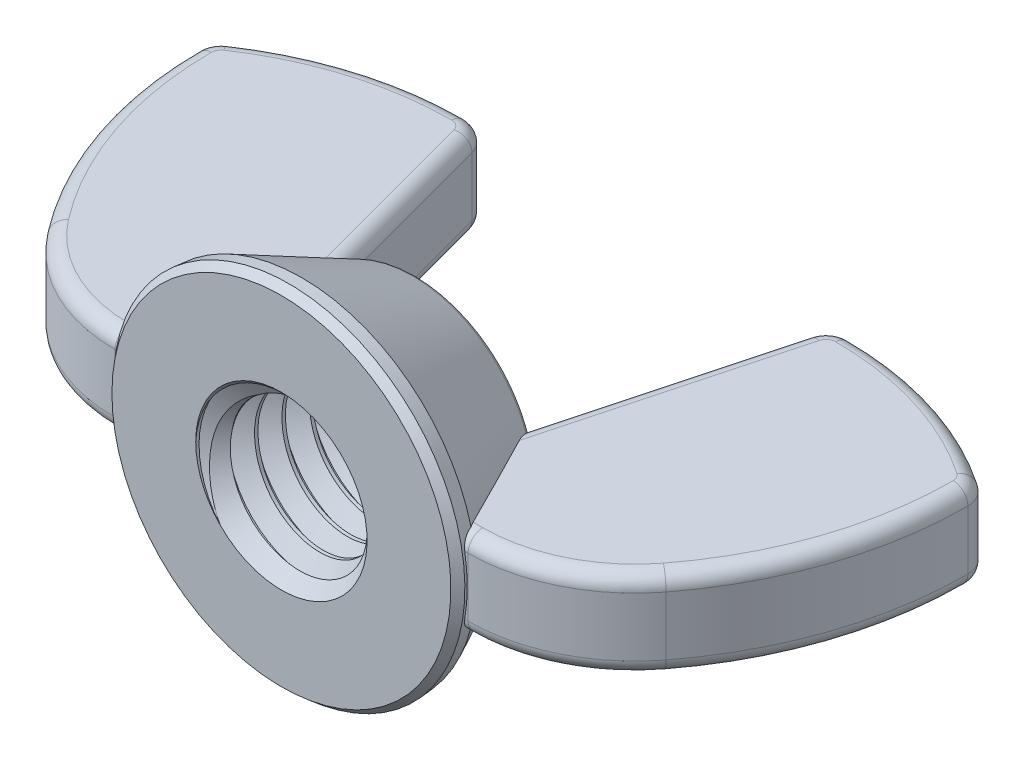
SolidWorks part; units mm, degrees
ref_plane "Front Plane" through (0, 0, 0) normal (0, 0, 1) x (1, 0, 0)
ref_plane "Top Plane" through (0, 0, 0) normal (0, 1, 0) x (1, 0, 0)
ref_plane "Right Plane" through (0, 0, 0) normal (1, 0, 0) x (0, 0, -1)
sketch "Sketch1" plane through (0, 0, 0) normal (0, 0, 1) x (1, 0, 0)
  circle A0 centre (0, 0) radius 2.5
  circle A1 centre (0, 0) radius 5.15
  dimension "D1" = 10.3
sketch "Sketch2" plane through (0, 0, 0) normal (0, 1, 0) x (1, 0, 0)
  line L0 (0, 0) -> (0, 11) construction
  line L1 (-2.5, 0) -> (2.5, 0) construction
  line L2 (-11.25, 11) -> (11.25, 11) construction
  line L3 (11.25, 11) -> (11.25, 0) construction
  line L4 (-11.25, 11) -> (-11.25, 0) construction
  line L5 (-11.25, 0) -> (11.25, 0) construction
  line L6 (-3.5176, 3.96) -> (3.5176, 3.96) construction
  line L7 (0, 0) -> (0, 3.96) construction
  line L8 (-4.3144, 0.594) -> (5.15, 0.594) construction
  line L9 (5.15, 0) -> (5.15, 3.96) construction
  line L10 (3.1659, 3.96) -> (5.1019, 11.1853)
  line L12 (3.5176, 3.96) -> (3.5176, 0.297) construction
  line L13 (-5.15, 0) -> (5.15, 0) construction
  line L14 (5.15, 0.594) -> (3.5176, 3.96) construction
  line L15 (5.1019, 11.1853) -> (11.5496, 9.214)
  line L16 (11.5496, 9.214) -> (7.1341, 0.297)
  line L17 (5.15, 0.297) -> (7.1341, 0.297)
  line L19 (3.1659, 0.297) -> (5.15, 0.297)
  line L20 (-3.1659, 3.96) -> (3.1659, 3.96) construction
  line L21 (3.1659, 3.96) -> (3.1659, 0.297)
  circle A3 centre (10.5347, 8.7764) radius 0.7153 construction
  circle A4 centre (5.6011, 10.2847) radius 0.7153 construction
  dimension "D6" = 1.4306
  dimension "D2" = 3.96
  dimension "D4" = 7.0353
  dimension "D1" = 0.594
  dimension "D3" = 25.871
  dimension "D5" = 0.297
  dimension "D8" = 17
  dimension "D9" = 6.3318
  dimension "D7" = 15
sketch "Sketch13" plane through (0, 0, 0) normal (0, 1, 0) x (1, 0, 0)
  line L1 (3.1659, 3.96) -> (3.1659, 0.297) construction
  line L2 (3.1659, 3.96) -> (5.1019, 11.1853) construction
  line L3 (-11.25, 11) -> (11.25, 11) construction
  line L4 (11.25, 11) -> (11.25, 0) construction
  line L5 (5.15, 0.297) -> (7.1341, 0.297) construction
  line L6 (3.1659, 0.297) -> (5.15, 0.297) construction
  line L7 (0, 0) -> (0, 3.96) construction
  line L8 (-2.5, 0) -> (2.5, 0) construction
  line L9 (0, 0) -> (0, 11) construction
  line L10 (-3.5176, 3.96) -> (3.5176, 3.96) construction
  line L11 (3.1659, 0.297) -> (5.15, 0.297)
  line L12 (3.1659, 3.96) -> (3.1659, 0.297)
  line L13 (3.1659, 3.96) -> (4.9102, 10.4698)
  circle A0 centre (10.5347, 8.7764) radius 0.7153 construction
  circle A1 centre (5.6011, 10.2847) radius 0.7153 construction
  arc A5 (11.25, 8.7764) -> (10.9347, 9.3694) centre (10.5347, 8.7764) ccw
  arc A6 (5.6011, 11) -> (4.9102, 10.4698) centre (5.6011, 10.2847) ccw
  arc A7 (9.0175, 2.2034) -> (11.25, 8.7764) centre (0.4576, 8.7764) ccw
  arc A8 (10.9347, 9.3694) -> (5.6011, 11) centre (5.6011, 1.462) ccw
  arc A10 (5.15, 0.297) -> (9.0175, 2.2034) centre (5.15, 5.1732) ccw
extrude "Extrude2" add sketch "Sketch13" along normal mid plane 2.575
sketch "Sketch3" plane through (0, 0, 0) normal (0, 0, 1) x (1, 0, 0)
  circle A0 centre (0, 0) radius 5.15 construction
  circle A1 centre (0, 0) radius 5.15
extrude "Extrude1" add sketch "Sketch3" against normal up to vertex (0.594 mm away) draft 5 separate body up to point (5.15, 0, -0.594)
sketch "Sketch15" plane through (0, 0, -0.594) normal (0, 0, -1) x (-1, 0, 0)
  circle A1 centre (0, 0) radius 5.098
  circle A2 centre (0, 0) radius 5.098
  dimension "D1" = 0
extrude "Extrude3" add sketch "Sketch15" along normal up to vertex (3.366 mm away) draft 25.871 up to point (0, 0, -3.96)
fillet "Fillet3" radius 0.254 1 edges at (-3.4657, 0, -3.96)
sketch "Sketch12" plane through (0, 0, -3.96) normal (0, 0, -1) x (-1, 0, 0)
  circle A1 centre (0, 0) radius 5.098
  circle A2 centre (0, 0) radius 5.098 construction
  dimension "D1" = 10.1961
sketch "Sketch4" plane through (0, 0, 0) normal (0, 0, 1) x (1, 0, 0)
  circle A0 centre (0, 0) radius 2.5 construction
  circle A1 centre (0, 0) radius 2.5
extrude "Cut-Extrude1" cut sketch "Sketch4" against normal through all
sketch "Sketch5" plane through (0, 0, 0) normal (0, 0, 1) x (1, 0, 0)
  circle A0 centre (0, 0) radius 2.5 construction
  circle A1 centre (0, 0) radius 2.5
curve "Helix/Spiral1" pitch 0.8 height 5.96 turns 7.45 parameters "pitch"=0.8
sketch "Sketch6" plane through (0, 0, 0) normal (0, 1, 0) x (1, 0, 0)
  line L0 (-2.5, -0.7) -> (-1.9804, -0.4)
  line L1 (-1.9804, -0.4) -> (-1.9804, -0.3)
  line L2 (-1.9804, -0.3) -> (-2.5, 0)
  line L3 (-2.5, -0.7) -> (-2.5, 0)
  line L4 (-2.5, -0.35) -> (-1.9804, -0.35) construction
  line L5 (-2.2402, -0.55) -> (-2.2402, -0.15) construction
  line L6 (-2.5, 0) -> (2.5, 0) construction
  dimension "D1" = 60
  dimension "D2" = 0.1
  dimension "D3" = 0.4
sweep "Sweep1" add profiles "Sketch6" path "Helix/Spiral1"
sketch "Sketch7" plane through (0, 0, 0) normal (0, 0, 1) x (1, 0, 0)
  circle A1 centre (0, 0) radius 5.15
  circle A2 centre (0, 0) radius 5.15
  dimension "D1" = 0
extrude "Cut-Extrude2" cut sketch "Sketch7" along normal through all
ref_plane "Plane1" through (0, 0, -3.96) normal (0, 0, 1) x (1, 0, 0)
sketch "Sketch8" plane through (0, 0, -3.96) normal (0, 0, 1) x (1, 0, 0)
  circle A0 centre (0, 0) radius 5.098 construction
  circle A2 centre (0, 0) radius 5.098
extrude "Cut-Extrude3" cut sketch "Sketch8" against normal through all
sketch "Sketch9" plane through (0, 0, 0) normal (0, 0, 1) x (1, 0, 0)
  circle A1 centre (0, 0) radius 2.5
  circle A2 centre (0, 0) radius 2.5
  dimension "D1" = 0
extrude "Cut-Extrude4" cut sketch "Sketch9" against normal through all draft 45
sketch "Sketch11" plane through (0, 0, -3.96) normal (0, 0, 1) x (1, 0, 0)
  circle A0 centre (0, 0) radius 2.5 construction
  circle A1 centre (0, 0) radius 2.4492
  circle A2 centre (0, 0) radius 2.5 construction
  dimension "D1" = 0.0508
extrude "Cut-Extrude5" cut sketch "Sketch11" along normal through all draft 45
chamfer "Chamfer1" distance 0.2228 angle 45 1 edges at (5.15, 0, 0)
fillet "Fillet4" radius 0.4292 14 edges at (4.1579, 1.2875, -0.297) (7.3059, 1.2875, -0.7995) (5.1657, 1.2875, -10.8522) (8.3897, 1.2875, -10.5832) (11.1663, 1.2875, -9.1122) (4.1579, -1.2875, -0.297) (7.3059, -1.2875, -0.7995) (5.1657, -1.2875, -10.8522) (8.3897, -1.2875, -10.5832) (11.1663, -1.2875, -9.1122) (10.6766, 1.2875, -5.3055) (10.6766, -1.2875, -5.3055) (4.038, 1.2875, -7.2149) (4.038, -1.2875, -7.2149)
mirror "Mirror6" about plane through (0, 0, 0) normal (1, 0, 0) of bodies 108 113
combine bodies "Combine2" operation type add bodies to combine 116 108 107
equation "\"D1@Sketch1\" = \"thread dia@Sketch1\"*1.725"
equation "\"D2@Sketch2\" = \"B@Sketch2\"*.36"
equation "\"D3@Helix/Spiral1\" = \"D2@Sketch2\"+2"
equation "\"D2@Sketch6\" = \"pitch@Helix/Spiral1\"*.125"
equation "\"D3@Sketch6\" = \"pitch@Helix/Spiral1\"*.5"
equation "\"D4@Sketch2\" = \"D1@Sketch12\"*.69"
equation "\"D1@Extrude2\" = \"D1@Sketch1\"*.25"
equation "\"D1@Sketch2\" = \"D2@Sketch2\"*.150"
equation "\"D5@Sketch2\" = \"D1@Sketch2\"/2"
equation "\"D3@Extrude3\" = \"D3@Sketch2\""
equation "\"D1@Chamfer1\" = \"D5@Sketch2\"*.75"
equation "\"D9@Sketch2\" = \"D4@Sketch2\"*.9"
equation "\"D6@Sketch2\" = \"D1@Extrude2\"/1.8"
equation "\"D1@Fillet4\" = \"D1@Extrude2\"/6"
